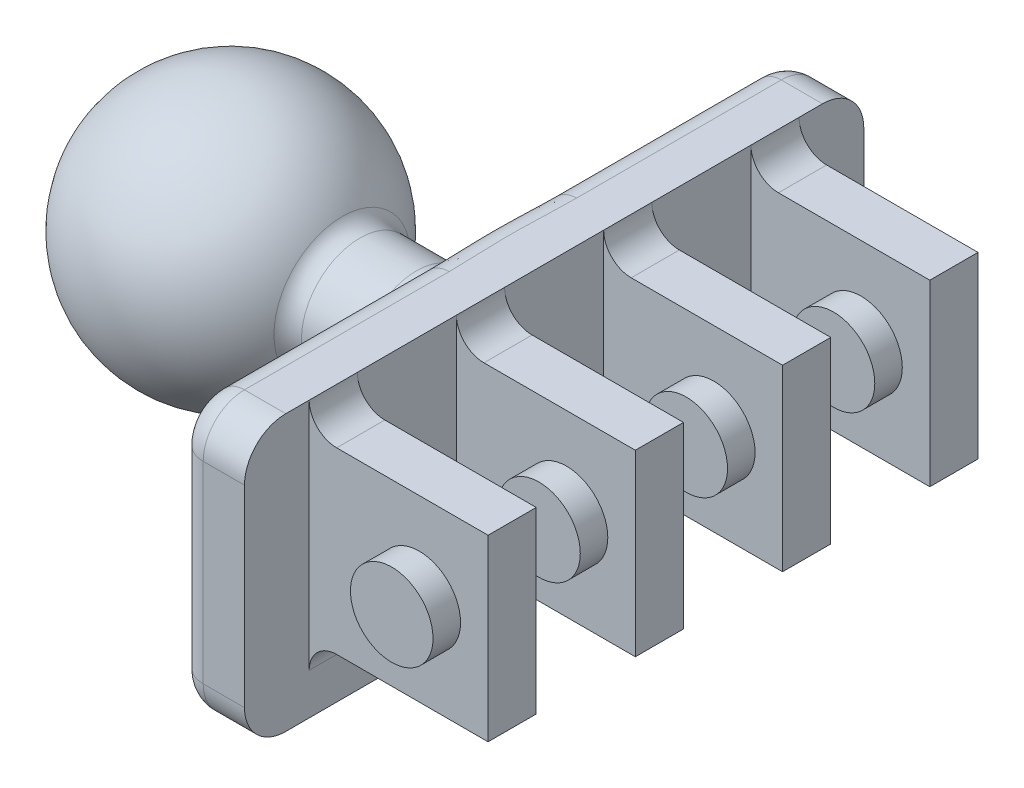
SolidWorks part; units mm, degrees
ref_plane "Front Plane" through (0, 0, 0) normal (0, 0, 1) x (1, 0, 0)
ref_plane "Top Plane" through (0, 0, 0) normal (0, 1, 0) x (1, 0, 0)
ref_plane "Right Plane" through (0, 0, 0) normal (1, 0, 0) x (0, 0, -1)
sketch "Sketch1" plane through (0, 0, 0) normal (0, 1, 0) x (1, 0, 0)
  line L0 (-9.5, 0) -> (8.5, 0)
  line L1 (8.5, 0) -> (8.5, 4.2426)
  arc A0 (8.5, 4.2426) -> (-9.5, 0) centre (0, 0) ccw
  dimension "D1" = 19
  dimension "D2" = 18
  dimension "D3" = 0
revolve "Revolve1" add sketch "Sketch1" angle 360 about L0
sketch "Sketch3" plane through (8.5, 0, 0) normal (1, 0, 0) x (0, 0, -1)
  circle A1 centre (0, 0) radius 4.2426
  circle A2 centre (0, 0) radius 4.2426
  dimension "D1" = 0
extrude "Boss-Extrude1" add sketch "Sketch3" along normal blind 10
fillet "Fillet1" radius 1.5 1 edges at (8.5, 0, -4.2426)
sketch "Sketch4" plane through (18.5, 0, 0) normal (1, 0, 0) x (0, 0, -1)
  line L1 (19.5, -10) -> (-19.5, -10)
  line L2 (22.5, -7) -> (22.5, 7)
  line L3 (19.5, 10) -> (-19.5, 10)
  line L4 (-22.5, -7) -> (-22.5, 7)
  line L5 (22.5, -10) -> (-22.5, 10) construction
  line L6 (22.5, 10) -> (-22.5, -10) construction
  arc A0 (-19.5, -10) -> (-22.5, -7) centre (-19.5, -7) cw
  arc A1 (19.5, -10) -> (22.5, -7) centre (19.5, -7) ccw
  arc A2 (22.5, 7) -> (19.5, 10) centre (19.5, 7) ccw
  arc A3 (-19.5, 10) -> (-22.5, 7) centre (-19.5, 7) ccw
  point P0 (0, 0)
  dimension "D3" = 3
  dimension "D1" = 45
  dimension "D2" = 20
extrude "Boss-Extrude2" add sketch "Sketch4" along normal blind 5
fillet "Fillet2" radius 5 1 edges at (18.5, 0, -4.2426)
sketch "Sketch5" plane through (0, 0, 22.5) normal (0, 0, 1) x (1, 0, 0)
  line L0 (23.5, 7) -> (23.5, -7) construction
  line L1 (23.5, 8) -> (36.5, 8)
  line L2 (23.5, 8) -> (23.5, -5)
  line L3 (23.5, -5) -> (36.5, -5)
  line L4 (36.5, 8) -> (36.5, -5)
  dimension "D1" = 13
  dimension "D2" = 13
  dimension "D3" = 8
extrude "Boss-Extrude3" add sketch "Sketch5" against normal through all
sketch "Sketch6" plane through (0, 8, 0) normal (0, 1, 0) x (1, 0, 0)
  line L0 (36.5, 22.5) -> (36.5, -22.5) construction
  line L1 (23.5, -22.5) -> (36.5, -22.5)
  line L2 (23.5, -22.5) -> (23.5, -17.8)
  line L3 (23.5, -17.8) -> (36.5, -17.8)
  line L4 (36.5, -22.5) -> (36.5, -17.8)
  line L5 (23.5, 19.5) -> (23.5, -19.5) construction
  line L6 (23.5, -14.3) -> (36.5, -14.3)
  line L7 (23.5, -14.3) -> (23.5, -7.1)
  line L8 (23.5, -7.1) -> (36.5, -7.1)
  line L9 (36.5, -14.3) -> (36.5, -7.1)
  line L10 (23.5, 22.3284) -> (23.5, -22.3284) construction
  line L11 (23.5, -3.6) -> (36.5, -3.6)
  line L12 (23.5, -3.6) -> (23.5, 3.6)
  line L13 (23.5, 3.6) -> (36.5, 3.6)
  line L14 (36.5, -3.6) -> (36.5, 3.6)
  line L16 (23.5, 7.1) -> (36.5, 7.1)
  line L17 (23.5, 7.1) -> (23.5, 14.3)
  line L18 (23.5, 14.3) -> (36.5, 14.3)
  line L19 (36.5, 7.1) -> (36.5, 14.3)
  line L20 (23.5, 17.8) -> (36.5, 17.8)
  line L21 (23.5, 17.8) -> (23.5, 22.5)
  line L22 (23.5, 22.5) -> (36.5, 22.5)
  line L23 (36.5, 17.8) -> (36.5, 22.5)
  dimension "D1" = 3.5
  dimension "D2" = 3.5
  dimension "D3" = 3.5
  dimension "D4" = 3.5
  dimension "D5" = 4.7
  dimension "D6" = 7.2
  dimension "D7" = 7.2
  dimension "D8" = 7.2
extrude "Cut-Extrude4" cut sketch "Sketch6" against normal up to next
sketch "Sketch9" plane through (0, 0, 17.8) normal (0, 0, 1) x (1, 0, 0)
  line L0 (36.5, -5) -> (23.5, -5) construction
  line L1 (36.5, -5) -> (36.5, 8) construction
  circle A0 centre (31.5, 1.5) radius 3
  dimension "D1" = 6
  dimension "D2" = 6.5
  dimension "D3" = 5
extrude "Boss-Extrude4" add sketch "Sketch9" along normal blind 2 and the other way blind 5.5
sketch "Sketch10" plane through (0, 0, 7.1) normal (0, 0, 1) x (1, 0, 0)
  circle A0 centre (31.5, 1.5) radius 3 construction
  circle A1 centre (31.5, 1.5) radius 3
extrude "Boss-Extrude5" add sketch "Sketch10" along normal blind 2 and the other way blind 5.5
sketch "Sketch12" plane through (0, 0, -3.6) normal (0, 0, 1) x (1, 0, 0)
  circle A0 centre (31.5, 1.5) radius 3 construction
  circle A1 centre (31.5, 1.5) radius 3
sketch "Sketch14" plane through (0, 0, -14.3) normal (0, 0, 1) x (1, 0, 0)
  circle A0 centre (31.5, 1.5) radius 3 construction
  circle A1 centre (31.5, 1.5) radius 3
extrude "Boss-Extrude6" add sketch "Sketch12" along normal blind 2 and the other way blind 5.5
extrude "Boss-Extrude7" add sketch "Sketch14" along normal blind 2 and the other way blind 5.5
fillet "Fillet4" radius 2 8 edges at (23.5, -5, -16.05) (23.5, -5, -5.35) (23.5, -5, 5.35) (23.5, -5, 16.05) (23.5, 8, -16.05) (23.5, 8, -5.35) (23.5, 8, 5.35) (23.5, 8, 16.05)
fillet "Fillet8" radius 2 8 edges at (18.5, 9.1213, -21.6213) (18.5, 0, -22.5) (18.5, -9.1213, -21.6213) (18.5, -10, 0) (18.5, -9.1213, 21.6213) (18.5, 0, 22.5) (18.5, 9.1213, 21.6213) (18.5, 10, 0)
